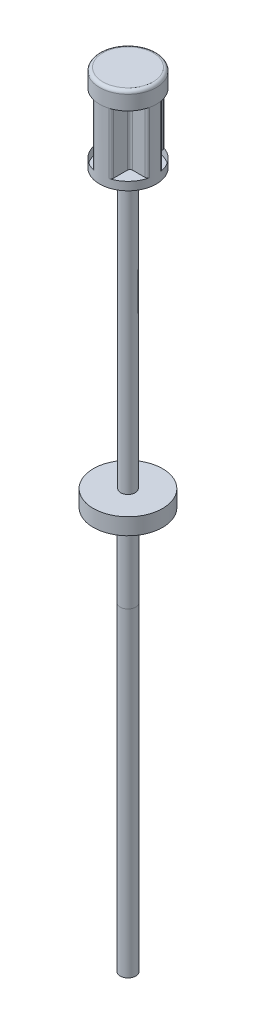
SolidWorks part; units mm, degrees
ref_plane "Front Plane" through (0, 0, 0) normal (0, 0, 1) x (1, 0, 0)
ref_plane "Top Plane" through (0, 0, 0) normal (0, 1, 0) x (1, 0, 0)
ref_plane "Right Plane" through (0, 0, 0) normal (1, 0, 0) x (0, 0, -1)
sketch "Sketch1" plane through (0, 0, 0) normal (0, 1, 0) x (1, 0, 0)
  line L0 (0, -1.045) -> (0, 1.045) construction
  circle A0 centre (0, 0) radius 0.95
  dimension "D1" = 1.9
sketch "Sketch2" plane through (0, 0, 0) normal (1, 0, 0) x (0, 0, -1)
  line L0 (0, 0) -> (0, 41.9)
  line L1 (0, 41.9) -> (0, 51.9)
  dimension "D1" = 41.9
  dimension "D2" = 10
sketch "Sketch3" plane through (0, 0, 0) normal (0, 1, 0) x (1, 0, 0)
sweep "Sweep1" add profiles "Sketch1" path "Sketch2"
sketch "Sketch4" plane through (0, 51.9, 0) normal (0, 1, 0) x (1, 0, 0)
  line L0 (0, 0) -> (0, -4.2)
  circle A0 centre (0, 0) radius 4.2
  dimension "D1" = 8.4
sketch "Sketch5" plane through (0, 0, 0) normal (1, 0, 0) x (0, 0, -1)
  line L0 (-4.2, 51.9) -> (-4.2, 53.9)
  line L1 (-4.2, 53.9) -> (0, 53.9)
  line L2 (0, 53.9) -> (0, 51.9)
  line L3 (-4.2, 51.9) -> (0, 51.9)
  dimension "D1" = 2
revolve "Revolve1" add sketch "Sketch5" angle 360 about L2 other way angle 360
sketch "Sketch6" plane through (0, 53.9, 0) normal (0, 1, 0) x (1, 0, 0)
  circle A0 centre (0, 0) radius 0.885
  dimension "D1" = 1.77
extrude "Boss-Extrude1" add sketch "Sketch6" along normal blind 33.75
sketch "Sketch7" plane through (0, 87.65, 0) normal (0, 1, 0) x (1, 0, 0)
  circle A0 centre (0, 0) radius 3.45
  dimension "D1" = 6.9
extrude "Boss-Extrude2" add sketch "Sketch7" along normal blind 1
sketch "Sketch8" plane through (0, 88.65, 0) normal (0, 1, 0) x (1, 0, 0)
  line L0 (1.2301, 0.8117) -> (1.2301, 3.2987)
  line L1 (4.0821, -0.9882) -> (1.2301, -0.9882)
  line L2 (4.0821, -0.9882) -> (4.0821, 0.8117)
  line L3 (4.0821, 0.8117) -> (1.2301, 0.8117)
  line L4 (-3.3532, -0.9882) -> (-3.3532, 0.8117)
  line L7 (1.2301, -4.0158) -> (-1.0104, -4.0158)
  line L8 (1.2301, -4.0158) -> (1.2301, -0.9882)
  line L9 (1.2301, 3.2987) -> (-1.0104, 3.2987)
  line L10 (-1.0104, -4.0158) -> (-1.0104, -0.9882)
  line L17 (-1.0104, -0.9882) -> (-3.3532, -0.9882)
  line L18 (-1.0104, 0.8117) -> (-1.0104, 3.2987)
  line L19 (-1.0104, 0.8117) -> (-3.3532, 0.8117)
  circle A0 centre (0, 0) radius 3.45 construction
  point P0 (0, 0)
  point P8 (0, 0)
sketch "Sketch9" plane through (0, 0, 0) normal (1, 0, 0) x (0, 0, -1)
  line L0 (0, 88.65) -> (0, 0)
  dimension "D1" = 88.65
extrude "Boss-Extrude3" add sketch "Sketch8" along normal blind 7.4 contours L1 L8 L7 L10 L17 L4 L19 L18 L9 L0 L3 L2
sketch "Sketch11" plane through (0, 96.05, 0) normal (0, 1, 0) x (1, 0, 0)
  circle A0 centre (0, 0) radius 3.45
  dimension "D1" = 6.9
extrude "Boss-Extrude4" add sketch "Sketch11" along normal blind 2.15
sketch "Sketch12" plane through (0, 96.05, 0) normal (0, 1, 0) x (1, 0, 0)
  circle A0 centre (0, 0) radius 3.4496
  circle A1 centre (0, 0) radius 5.0531
extrude "Cut-Extrude1" cut sketch "Sketch12" against normal blind 10
fillet "Fillet4" radius 0.4 1 edges at (0, 98.2, 3.45)
fillet "Fillet5" radius 0.3 12 edges at (1.2301, 92.35, -3.2228) (-1.0104, 92.35, -3.2983) (-1.0104, 92.35, -0.8117) (-3.3527, 92.35, -0.8117) (-3.305, 92.35, 0.9882) (-1.0104, 92.35, 0.9882) (-1.0104, 92.35, 3.2983) (1.2301, 92.35, 3.2228) (3.305, 92.35, 0.9882) (3.3527, 92.35, -0.8117) (1.2301, 92.35, -0.8117) (1.2301, 92.35, 0.9882)
sketch "Sketch19" plane through (0, 0, 0) normal (0, -1, 0) x (1, 0, 0)
  circle A1 centre (0, 0) radius 0.95
  circle A2 centre (0, 0) radius 0.95
  dimension "D1" = 0
sketch "Sketch15" plane through (0, 0, 0) normal (0, -1, 0) x (1, 0, 0)
  circle A0 centre (0, 0) radius 0.95
extrude "Cut-Extrude2" cut sketch "Sketch15" against normal blind 3.09
